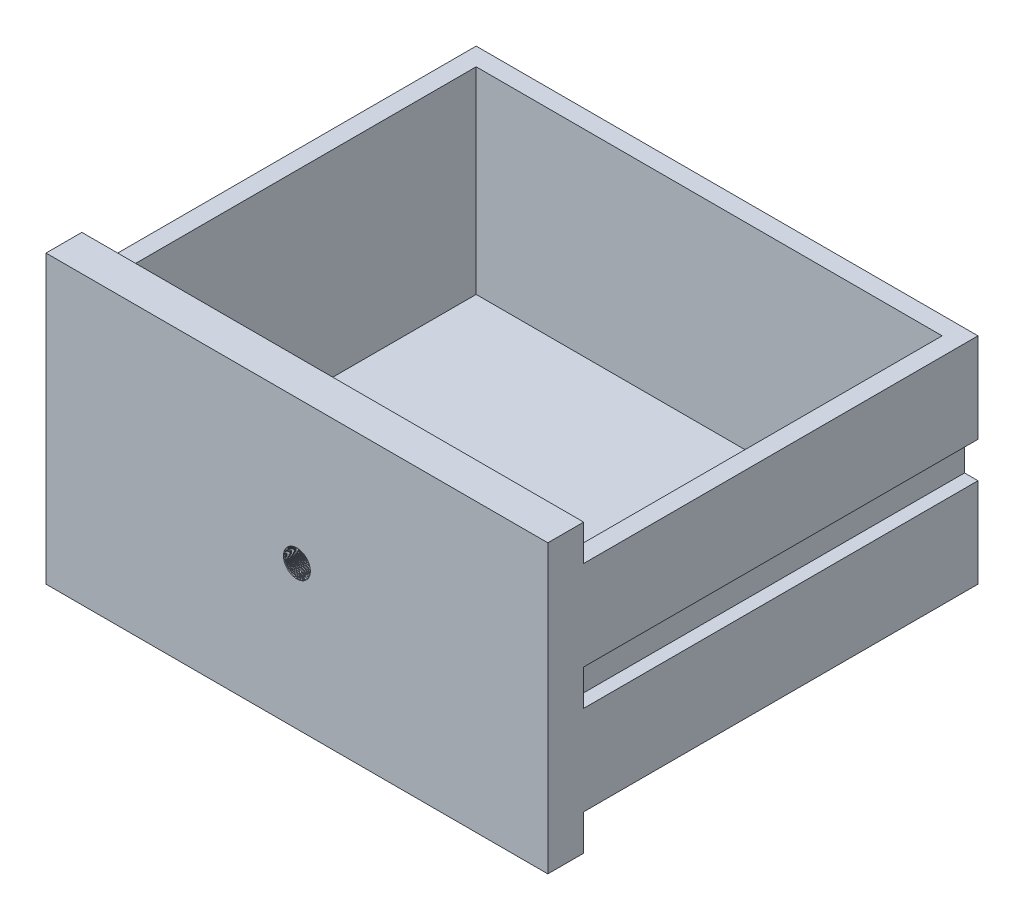
SolidWorks part; units mm, degrees
ref_plane "Front Plane" through (0, 0, 0) normal (0, 0, 1) x (1, 0, 0)
ref_plane "Top Plane" through (0, 0, 0) normal (0, 1, 0) x (1, 0, 0)
ref_plane "Right Plane" through (0, 0, 0) normal (1, 0, 0) x (0, 0, -1)
sketch "Sketch1" plane through (0, 0, 0) normal (0, 0, 1) x (1, 0, 0)
  line L1 (-177.8, -101.6) -> (177.8, -101.6)
  line L2 (-177.8, -101.6) -> (-177.8, 101.6)
  line L3 (-177.8, 101.6) -> (177.8, 101.6)
  line L4 (177.8, -101.6) -> (177.8, 101.6)
  line L5 (-177.8, -101.6) -> (177.8, 101.6) construction
  line L6 (-177.8, 101.6) -> (177.8, -101.6) construction
  point P0 (0, 0)
  dimension "D1" = 203.2
  dimension "D2" = 355.6
extrude "Boss-Extrude1" add sketch "Sketch1" against normal blind 25.4
sketch "Sketch2" plane through (0, 0, -25.4) normal (0, 0, -1) x (-1, 0, 0)
  line L0 (-177.8, -101.6) -> (-177.8, 101.6) construction
  line L1 (-177.8, -76.2) -> (177.8, -76.2)
  line L2 (-177.8, -76.2) -> (-177.8, 76.2)
  line L3 (-177.8, 76.2) -> (177.8, 76.2)
  line L4 (177.8, -76.2) -> (177.8, 76.2)
  line L5 (-177.8, -76.2) -> (177.8, 76.2) construction
  line L6 (-177.8, 76.2) -> (177.8, -76.2) construction
  point P0 (0, 0)
  dimension "D1" = 152.4
extrude "Boss-Extrude2" add sketch "Sketch2" along normal blind 279.4
shell "Shell1" thickness 12.7
sketch "Sketch3" plane through (0, 0, -304.8) normal (0, 0, -1) x (-1, 0, 0)
  line L0 (-177.8, 76.2) -> (-177.8, -76.2) construction
  line L1 (-187.325, -12.7) -> (-168.275, -12.7)
  line L2 (-187.325, -12.7) -> (-187.325, 12.7)
  line L3 (-187.325, 12.7) -> (-168.275, 12.7)
  line L4 (-168.275, -12.7) -> (-168.275, 12.7)
  line L5 (-187.325, -12.7) -> (-168.275, 12.7) construction
  line L6 (-187.325, 12.7) -> (-168.275, -12.7) construction
  line L7 (0, 18.4099) -> (0, -16.2007) construction
  line L8 (168.275, -12.7) -> (168.275, 12.7)
  line L9 (187.325, -12.7) -> (168.275, -12.7)
  line L10 (187.325, -12.7) -> (187.325, 12.7)
  line L11 (187.325, 12.7) -> (168.275, 12.7)
  point P0 (-177.8, 0)
  dimension "D1" = 25.4
  dimension "D2" = 19.05
extrude "Cut-Extrude1" cut sketch "Sketch3" against normal blind 279.4
sketch "Sketch4" plane through (0, 0, 0) normal (0, 0, 1) x (1, 0, 0)
  circle A0 centre (0, 0) radius 9.525
  dimension "D1" = 19.05
extrude "Cut-Extrude2" cut sketch "Sketch4" against normal up to next
thread "Thread1" pitch 0.7937 profile "Thread Profile1" start angle 0, offset 0, length 25.4, pitch 0.7937, diameter 19.05
ref_plane "Plane1" through (-9.525, 0, 0) normal (0, -1, 0) x (-1, 0, 0)
sketch "Thread Profile1" plane through (-9.525, 0, 0) normal (0, -1, 0) x (-1, 0, 0)
  line L0 (0, 0) -> (0, 0.7937) construction
  line L11 (0, 0) -> (0, 0.6945)
  line L12 (0, 0.6945) -> (-0.4296, 0.4465)
  line L13 (-0.4296, 0.4465) -> (-0.4296, 0.248)
  line L15 (-0.4296, 0.248) -> (0, 0)
  line L17 (-0.4296, 0.3473) -> (0, 0.3473) construction
  point P2 (0, 0)
  dimension "Pitch" = 0.7937
  dimension "Profile_Angle" = 60
  dimension "Profile_Land" = 0.1984
  dimension "Profile_Height" = 0.4296
scale "Scale1" scale about centroid uniform scaling yes scale factor 0.75
